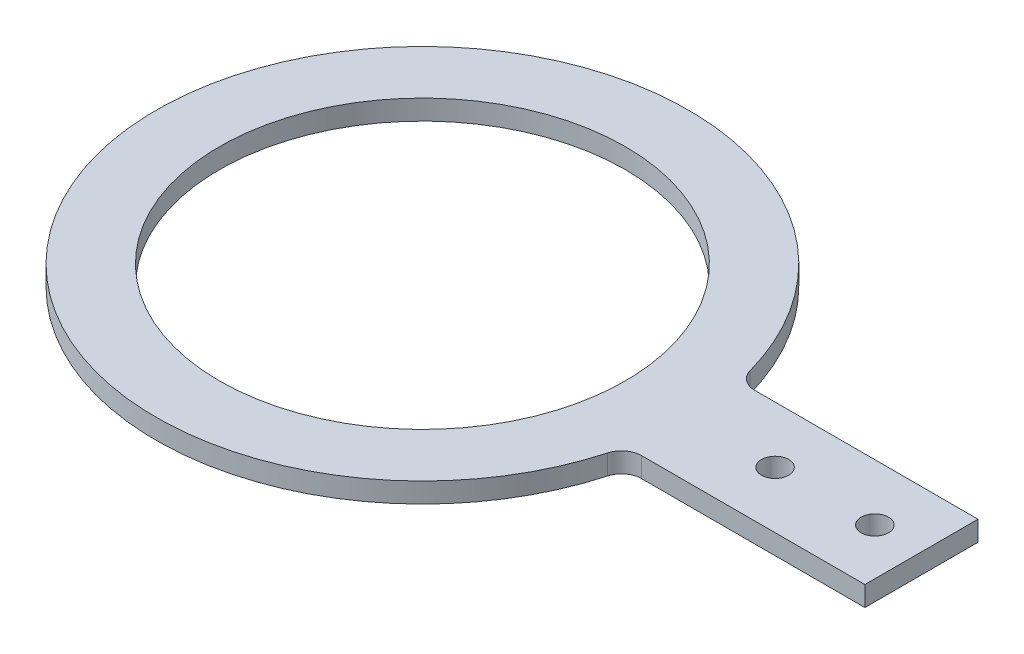
SolidWorks part; units mm, degrees
ref_plane "Front Plane" through (0, 0, 0) normal (0, 0, 1) x (1, 0, 0)
ref_plane "Top Plane" through (0, 0, 0) normal (0, 1, 0) x (1, 0, 0)
ref_plane "Right Plane" through (0, 0, 0) normal (1, 0, 0) x (0, 0, -1)
sketch "Sketch1" plane through (0, 0, 0) normal (0, 1, 0) x (1, 0, 0)
  circle A0 centre (0, 0) radius 40
  circle A1 centre (0, 0) radius 30.5
  dimension "D1" = 80
  dimension "D2" = 61
extrude "Boss-Extrude1" add sketch "Sketch1" along normal blind 3
sketch "Sketch2" plane through (0, 3, 0) normal (0, 1, 0) x (1, 0, 0)
  line L1 (35, 8.5) -> (75, 8.5)
  line L2 (35, 8.5) -> (35, -8.5)
  line L3 (35, -8.5) -> (75, -8.5)
  line L4 (75, 8.5) -> (75, -8.5)
  circle A0 centre (0, 0) radius 30.5 construction
  dimension "D1" = 17
  dimension "D2" = 8.5
  dimension "D3" = 35
  dimension "D4" = 40
extrude "Boss-Extrude2" add sketch "Sketch2" against normal up to surface (3 mm away) up to face at (0, 0, 40)
sketch "Sketch3" plane through (0, 3, 0) normal (0, 1, 0) x (1, 0, 0)
  line L0 (75, -8.5) -> (75, 8.5) construction
  circle A0 centre (53, 0) radius 2.05
  circle A1 centre (68, 0) radius 2.05
  point P6 (0, 0)
  point P7 (0, 0)
  dimension "D1" = 4.1
  dimension "D2" = 15
  dimension "D3" = 7
extrude "Cut-Extrude1" cut sketch "Sketch3" against normal through all
fillet "Fillet1" radius 3 2 edges at (39.0864, 1.5, 8.5) (39.0864, 1.5, -8.5)
